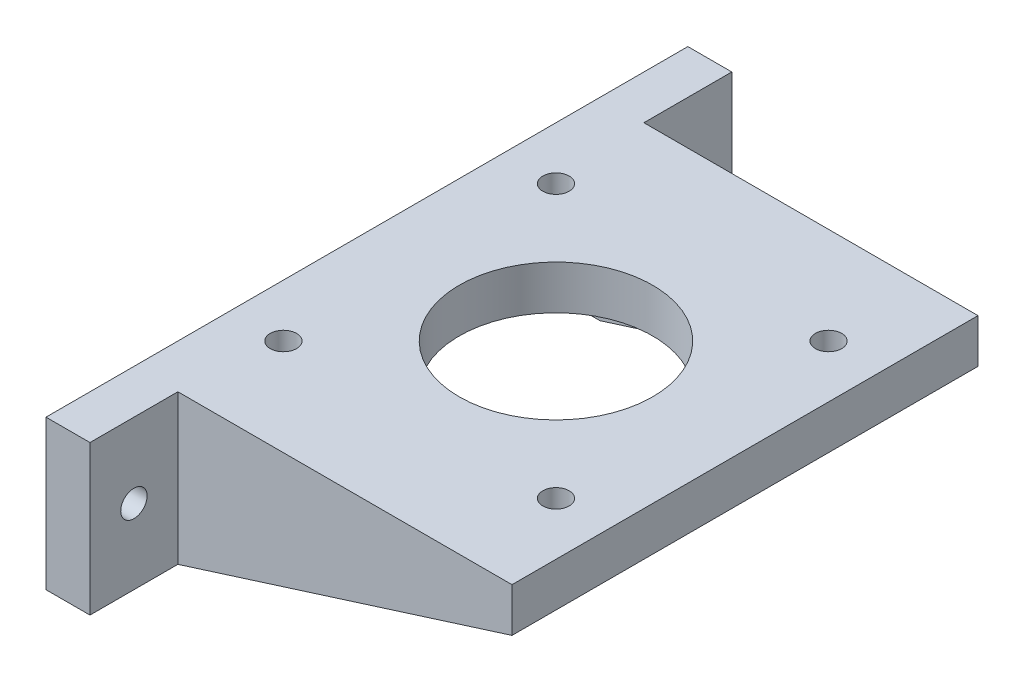
SolidWorks part; units mm, degrees
material "ABS"
ref_plane "Front Plane" through (0, 0, 0) normal (0, 0, 1) x (1, 0, 0)
ref_plane "Top Plane" through (0, 0, 0) normal (0, 1, 0) x (1, 0, 0)
ref_plane "Right Plane" through (0, 0, 0) normal (1, 0, 0) x (0, 0, -1)
sketch "Sketch1" plane through (0, 0, 0) normal (0, 0, 1) x (1, 0, 0)
  line L0 (5, 5) -> (43, 5)
  line L1 (0, 0) -> (5, 0)
  line L2 (0, 0) -> (0, 5)
  line L3 (0, 5) -> (5, 5)
  line L4 (5, 0) -> (5, 5)
  line L5 (43, 5) -> (43, 0)
  line L6 (43, 0) -> (5, 0)
  line L7 (5, 0) -> (5, -12)
  line L8 (5, -12) -> (0, -12)
  line L9 (0, -12) -> (0, 0)
  line L10 (5, -12) -> (43, 0)
  dimension "D1" = 5
  dimension "D2" = 5
  dimension "D3" = 43
  dimension "D4" = 12
extrude "Boss-Extrude1" add sketch "Sketch1" against normal blind 43 contours L1 L4 L3 L2 | L6 L5 L0 L4 region at (2.5, 2.5, 0) region at (24, 2.5, 0)
sketch "Sketch2" plane through (0, 5, 0) normal (0, 1, 0) x (1, 0, 0)
  line L3 (0, 43) -> (0, 0) construction
  line L4 (0, 0) -> (43, 0) construction
  circle A0 centre (21.5, 21.5) radius 11
  circle A1 centre (37, 37) radius 1.5
  circle A2 centre (6, 37) radius 1.5
  circle A3 centre (6, 6) radius 1.5
  circle A4 centre (37, 6) radius 1.5
  dimension "D3" = 22
  dimension "D4" = 3
  dimension "D1" = 21.5
  dimension "D2" = 21.5
  dimension "D5" = 15.5
  dimension "D6" = 15.5
  dimension "D7" = 2
  dimension "D8" = 2
extrude "Cut-Extrude1" cut sketch "Sketch2" against normal through all
extrude "Boss-Extrude2" add sketch "Sketch1<3>" along normal blind 5 contours L7 L10 L6 | L6 L5 L0 L4 | L1 L4 L3 L2 | L9 L8 L7 L1 region at (2.5, 2.5, 0) region at (24, 2.5, 0) region at (2.5, -6, 0) region at (17.6667, -4, 0)
sketch "Sketch1<3>" plane through (0, 0, 0) normal (0, 0, 1) x (1, 0, 0) same geometry as "Sketch1"
extrude "Boss-Extrude3" add sketch "Sketch1<4>" against normal blind 5 from vertex contours L1 L4 L3 L2 | L9 L8 L7 L1 | L7 L10 L6 | L6 L5 L0 L4 region at (2.5, 2.5, 0) region at (24, 2.5, 0) region at (2.5, -6, 0) region at (17.6667, -4, 0) starting at point (0, 5, -43)
sketch "Sketch1<4>" plane through (0, 0, 0) normal (0, 0, 1) x (1, 0, 0) same geometry as "Sketch1"
sketch "Sketch3" plane through (0, 0, 0) normal (-1, 0, 0) x (0, 0, 1)
  line L0 (5, -12) -> (0, -12) construction
  line L1 (5, 5) -> (15, 5)
  line L2 (5, 5) -> (5, -12)
  line L3 (5, -12) -> (15, -12)
  line L4 (15, 5) -> (15, -12)
  line L5 (10, 5) -> (10, -12) construction
  line L6 (15, -3.5) -> (5, -3.5) construction
  line L7 (-21.5, 5) -> (-21.5, 0) construction
  line L8 (-48, 5) -> (5, 5) construction
  line L9 (-43, 0) -> (0, 0) construction
  line L10 (-48, -12) -> (-58, -12)
  line L11 (-58, 5) -> (-58, -12)
  line L12 (-53, 5) -> (-53, -12) construction
  line L13 (-58, -3.5) -> (-48, -3.5) construction
  line L14 (-48, 5) -> (-48, -12)
  line L15 (-48, 5) -> (-58, 5)
  circle A0 centre (10, -3.5) radius 1.5
  circle A1 centre (-53, -3.5) radius 1.5
  dimension "D2" = 3
  dimension "D1" = 10
extrude "Boss-Extrude4" add sketch "Sketch3" against normal blind 5
equation "\"rod_diameter\"= 8"
equation "\"rod_hole_thickness\"= 4"
equation "\"rod_radius\"= \"rod_diameter\" / 2"
equation "\"platter_diameter\"= 320"
equation "\"platter_radius\"= \"platter_diameter\" / 2"
equation "\"extruder_mount_hole_spacing\"= 75"
equation "\"arm_rod_spacing\"= 40"
equation "\"D2@Sketch2\" = \"D1@Boss-Extrude1\" / 2"
equation "\"motor_level_rod_spacing\"= 15"
equation "\"top_frame_spacing\"= 90"
equation "\"linear_bearing_diameter\"= 15"
equation "\"z_rod_spacing\"= 75"
equation "\"platter_rod_spacing\"= 50"
equation "\"rod_nut_thickness\"= 6.5"
equation "\"rod_nut_inscribed_diameter\"= 13"
equation "\"z_height\"= 350"
equation "\"gear_pitch\"=2"
equation "\"r_gear_teeth\"= 450"
equation "\"theta_gear_teeth\"= 385"
equation "\"sheet_thickness\"=5"
equation "\"sheet_tab_hole_thickness\"= \"sheet_thickness\""
equation "\"sheet_tab_width\"= \"sheet_thickness\"*2"
equation "\"sheet_bolt_diameter\"= 3"
equation "\"sheet_bolt_length\"= 16"
equation "\"sheet_nut_diameter\"= 5.5"
equation "\"sheet_nut_thickness\"= 2.5"
equation "\"sheet_nut_depth\"= 10"
equation "\"bearing_outside_diameter\"= 22"
equation "\"bearing_thickness\"= 7"
equation "\"corner_part_thickness\"= \"sheet_thickness\" + \"bearing_thickness\""
equation "\"D4@Sketch1\"=\"sheet_thickness\"*2+7-\"D1@Sketch1\""
equation "\"D1@Sketch2\"= \"D3@Sketch1\" / 2"
equation "\"D1@Sketch3\"=\"sheet_thickness\"*2"
equation "\"D2@Sketch3\"=\"sheet_bolt_diameter\""
